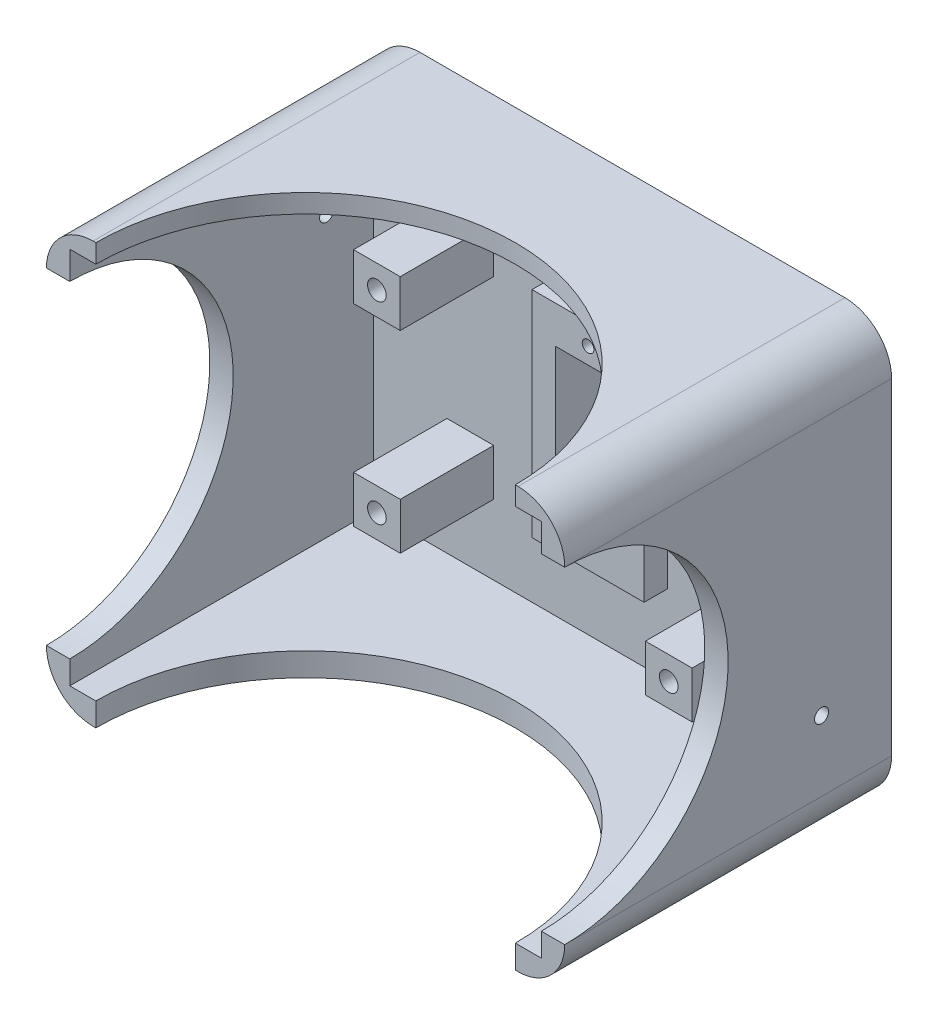
SolidWorks part; units mm, degrees
ref_plane "Plan de face" through (0, 0, 0) normal (0, 0, 1) x (1, 0, 0)
ref_plane "Plan de dessus" through (0, 0, 0) normal (0, 1, 0) x (1, 0, 0)
ref_plane "Plan de droite" through (0, 0, 0) normal (1, 0, 0) x (0, 0, -1)
sketch "Esquisse1" plane through (0, 0, 0) normal (0, 0, 1) x (1, 0, 0)
  line L0 (-192.776, 43.0961) -> (-152.776, 47.5961)
  line L1 (-152.776, 47.5961) -> (115.224, 47.5961)
  line L2 (-152.776, 47.5961) -> (-152.776, -102.4039)
  line L3 (-152.776, -102.4039) -> (115.224, -102.4039)
  line L4 (115.224, 47.5961) -> (115.224, -102.4039)
  line L5 (-152.776, 47.5961) -> (-192.776, 47.5961)
  line L6 (-152.776, 53.8314) -> (-152.776, -102.4039)
  line L7 (-152.776, 47.5961) -> (-152.776, -102.4039)
  line L8 (-152.776, -102.4039) -> (-192.776, -102.4039)
  line L9 (-192.776, 47.5961) -> (-192.776, -102.4039)
  line L10 (-152.776, 47.5961) -> (-192.776, 47.5961)
  line L11 (-152.776, 47.5961) -> (-152.776, 43.0961)
  line L12 (-152.776, 43.0961) -> (-192.776, 43.0961)
  line L13 (-192.776, 47.5961) -> (-192.776, 43.0961)
  line L14 (-152.776, -102.4039) -> (-192.776, -102.4039)
  line L15 (-152.776, -102.4039) -> (-152.776, -97.9039)
  line L16 (-152.776, -97.9039) -> (-192.776, -97.9039)
  line L17 (-192.776, -102.4039) -> (-192.776, -97.9039)
  line L18 (-192.776, -97.9039) -> (-152.776, -102.4039)
  line L20 (-106.994, -67.4039) -> (-5.994, -67.4039)
  line L21 (-106.994, -67.4039) -> (-106.994, 13.5961)
  line L22 (-106.994, 13.5961) -> (-5.994, 13.5961)
  line L23 (-5.994, -67.4039) -> (-5.994, 13.5961)
  line L24 (-144.9874, 47.5961) -> (-124.9874, 47.5961)
  line L25 (-144.9874, 47.5961) -> (-144.9874, 45.5961)
  line L26 (-144.9874, 45.5961) -> (-124.9874, 45.5961)
  line L27 (-124.9874, 47.5961) -> (-124.9874, 45.5961)
  line L28 (-144.9874, -102.4039) -> (-124.9874, -102.4039)
  line L29 (-144.9874, -102.4039) -> (-144.9874, -100.4039)
  line L30 (-144.9874, -100.4039) -> (-124.9874, -100.4039)
  line L31 (-124.9874, -102.4039) -> (-124.9874, -100.4039)
  line L32 (-111.994, -72.4039) -> (-0.994, -72.4039)
  line L33 (-111.994, -72.4039) -> (-111.994, 17.5961)
  line L34 (-111.994, 17.5961) -> (-0.994, 17.5961)
  line L35 (-0.994, -72.4039) -> (-0.994, 17.5961)
  line L36 (-101.994, 7.5961) -> (-10.994, 7.5961)
  line L37 (-101.994, 7.5961) -> (-101.994, -62.4039)
  line L38 (-101.994, -62.4039) -> (-10.994, -62.4039)
  line L39 (-10.994, 7.5961) -> (-10.994, -62.4039)
  line L40 (-48.994, -12.4039) -> (-62.994, -12.4039)
  line L41 (-48.994, -12.4039) -> (-48.994, -42.4039)
  line L42 (-48.994, -42.4039) -> (-62.994, -42.4039)
  line L43 (-62.994, -12.4039) -> (-62.994, -42.4039)
  line L44 (-101.994, 7.5961) -> (-91.994, 7.5961)
  line L45 (-101.994, 7.5961) -> (-101.994, -2.4039)
  line L46 (-91.2204, -1.1134) -> (-81.2204, -1.1134)
  line L47 (-91.2204, -1.1134) -> (-91.2204, -11.1134)
  line L48 (-101.994, -62.4039) -> (-91.994, -62.4039)
  line L49 (-101.994, -62.4039) -> (-101.994, -52.4039)
  line L50 (-91.2204, -11.1134) -> (-81.2204, -11.1134)
  line L51 (-81.2204, -1.1134) -> (-81.2204, -11.1134)
  line L52 (-10.994, -62.4039) -> (-20.994, -62.4039)
  line L53 (-10.994, -62.4039) -> (-10.994, -52.4039)
  line L54 (-28.7204, -1.16) -> (-18.7204, -1.16)
  line L55 (-28.7204, -1.16) -> (-28.7204, -11.16)
  line L56 (-10.994, 7.5961) -> (-20.994, 7.5961)
  line L57 (-10.994, 7.5961) -> (-10.994, -2.4039)
  line L58 (-28.7204, -11.16) -> (-18.7204, -11.16)
  line L59 (-18.7204, -1.16) -> (-18.7204, -11.16)
  line L60 (-67.994, -50.4039) -> (-43.994, -50.4039)
  line L61 (-67.994, -50.4039) -> (-67.994, -4.4039)
  line L62 (-67.994, -4.4039) -> (-43.994, -4.4039)
  line L63 (-43.994, -50.4039) -> (-43.994, -4.4039)
  line L64 (-28.7144, -42.46) -> (-18.7144, -42.46)
  line L65 (-28.7144, -42.46) -> (-28.7144, -52.46)
  line L66 (-28.7144, -52.46) -> (-18.7144, -52.46)
  line L67 (-18.7144, -42.46) -> (-18.7144, -52.46)
  line L68 (-91.2144, -42.4134) -> (-81.2144, -42.4134)
  line L69 (-91.2144, -42.4134) -> (-91.2144, -52.4134)
  line L70 (-91.2144, -52.4134) -> (-81.2144, -52.4134)
  line L71 (-81.2144, -42.4134) -> (-81.2144, -52.4134)
  arc A0 (115.224, -102.4039) -> (115.224, 47.5961) centre (-162.1791, -27.4039) ccw
  arc A1 (-192.776, -97.9039) -> (-192.776, 43.0961) centre (-63.7022, -27.4039) cw
  circle A2 centre (-215.7698, -27.1553) radius 2.5
  circle A3 centre (130.2178, -27.1553) radius 2.5
  circle A4 centre (-33.549, -107.4039) radius 2.5
  circle A5 centre (-33.549, 52.5961) radius 2.5
  circle A6 centre (-86.2204, -6.1134) radius 2
  circle A7 centre (-23.7204, -6.16) radius 2
  circle A8 centre (-86.2144, -47.4134) radius 2
  circle A9 centre (-23.7144, -47.46) radius 2
  circle A10 centre (-55.994, -45.9039) radius 1.25
  circle A11 centre (-55.994, -8.9039) radius 1.25
  point P11 (-210.776, -27.4039)
  point P12 (125.224, -27.4039)
  point P35 (-56.494, 17.5961)
  dimension "D10" = 30
  dimension "D19" = 5
  dimension "D48" = 62.5
  dimension "D60" = 37
  dimension "D1" = 268
  dimension "D2" = 150
  dimension "D3" = 40
  dimension "D4" = 4.5
  dimension "D5" = 4.5
  dimension "D6" = 18
  dimension "D7" = 75
  dimension "D8" = 10
  dimension "D9" = 75
  dimension "D11" = 81
  dimension "D12" = 35
  dimension "D13" = 48
  dimension "D14" = 2
  dimension "D15" = 20
  dimension "D16" = 20
  dimension "D17" = 2
  dimension "D18" = 48
  dimension "D20" = 30
  dimension "D21" = 5
  dimension "D22" = 5
  dimension "D23" = 5
  dimension "D24" = 34
  dimension "D25" = 101
  dimension "D26" = 5
  dimension "D27" = 5
  dimension "D28" = 10
  dimension "D29" = 5
  dimension "D30" = 5
  dimension "D31" = 5
  dimension "D32" = 14
  dimension "D33" = 30
  dimension "D34" = 38
  dimension "D35" = 10
  dimension "D36" = 5
  dimension "D37" = 5
  dimension "D38" = 10
  dimension "D39" = 10
  dimension "D40" = 5
  dimension "D41" = 5
  dimension "D42" = 10
  dimension "D43" = 20
  dimension "D44" = 5
  dimension "D45" = 8
  dimension "D46" = 5
  dimension "D47" = 8
  dimension "D49" = 62.5
  dimension "D50" = 41.3
  dimension "D51" = 41.3
  dimension "D52" = 62.5
  dimension "D53" = 10
  dimension "D54" = 5
  dimension "D55" = 5
  dimension "D56" = 10
  dimension "D57" = 10
  dimension "D58" = 5
  dimension "D59" = 5
  dimension "D61" = 7
  dimension "D62" = 3.5
  dimension "D63" = 7
extrude "Boss.-Extru.1" add sketch "Esquisse1" along normal blind 70 contours L32 L35 L34 L33 L23 L20 L21 L22 region at (-110.565, -27.4039, 0)
extrude "Boss.-Extru.2" add sketch "Esquisse1<35>" along normal blind 5 contours L20 L23 L22 L21 L36 L39 L38 L37 | L39 L36 L37 L38 region at (-105.6993, -26.9039, 0) region at (-96.994, 6.448, 0)
sketch "Esquisse1<35>" plane through (0, 0, 0) normal (0, 0, 1) x (1, 0, 0) same geometry as "Esquisse1"
extrude "Boss.-Extru.5" add sketch "Esquisse1<37>" along normal blind 1 contours L36 L37 region at (-96.994, 6.448, 0)
sketch "Esquisse1<37>" plane through (0, 0, 0) normal (0, 0, 1) x (1, 0, 0) same geometry as "Esquisse1"
extrude "Boss.-Extru.6" add sketch "Esquisse1<38>" along normal blind 5 contours L38 L37 | L38 L39 | L36 L39 region at (-96.994, 6.448, 0)
sketch "Esquisse1<38>" plane through (0, 0, 0) normal (0, 0, 1) x (1, 0, 0) same geometry as "Esquisse1"
fillet "Congé1" radius 10 1 edges at (-111.994, -72.4039, 35)
fillet "Congé2" radius 10 1 edges at (-111.994, 17.5961, 35)
fillet "Congé4" radius 10 1 edges at (-0.994, 17.5961, 35)
fillet "Congé5" radius 10 1 edges at (-0.994, -72.4039, 35)
sketch "Esquisse3" plane through (0, -72.4039, 0) normal (0, -1, 0) x (1, 0, 0)
  line L0 (-101.994, 70) -> (-10.994, 70) construction
  circle A0 centre (-56.494, 70) radius 44.9177
extrude "Enlèv. mat.-Extru.2" cut sketch "Esquisse3" against normal blind 111 contours A0
sketch "Esquisse4" plane through (-0.994, 0, 0) normal (1, 0, 0) x (0, 0, -1)
  line L0 (-70, -62.4039) -> (-70, 7.5961) construction
  circle A0 centre (-70, -27.4039) radius 35
extrude "Enlèv. mat.-Extru.3" cut sketch "Esquisse4" against normal blind 111 contours A0
sketch "Esquisse5" plane through (-111.994, 0, 0) normal (-1, 0, 0) x (0, 0, 1)
  line L0 (70, 7.5961) -> (0, 7.5961) construction
  line L1 (0, -62.4039) -> (0, 7.5961) construction
  circle A0 centre (15, -7.4039) radius 1.5
  dimension "D1" = 15
  dimension "D2" = 15
extrude "Enlèv. mat.-Extru.6" cut sketch "Esquisse5" against normal blind 5
sketch "Esquisse8" plane through (-0.994, 0, 0) normal (1, 0, 0) x (0, 0, -1)
  line L0 (-70, -62.4039) -> (0, -62.4039) construction
  line L1 (0, -62.4039) -> (0, 7.5961) construction
  circle A0 centre (-15, -47.4039) radius 1.5
  dimension "D1" = 15
  dimension "D2" = 15
extrude "Enlèv. mat.-Extru.7" cut sketch "Esquisse8" against normal blind 15 contours A0
extrude "Boss.-Extru.9" add sketch "Esquisse1<44>" along normal blind 10 contours L60 L63 L62 L61 L43 L40 L41 L42 region at (-67.4751, -27.4039, 0)
sketch "Esquisse1<44>" plane through (0, 0, 0) normal (0, 0, 1) x (1, 0, 0) same geometry as "Esquisse1"
extrude "Boss.-Extru.10" add sketch "Esquisse1<45>" along normal blind 25 contours L51 L46 L47 L50 A6 | L71 L68 L69 L70 A8 | L59 L54 L55 L58 A7 | L67 L64 L65 L66 A9 region at (-86.2204, -1.2548, 0) region at (-23.7204, -1.3014, 0) region at (-23.7144, -42.6014, 0) region at (-86.2144, -42.5548, 0)
sketch "Esquisse1<45>" plane through (0, 0, 0) normal (0, 0, 1) x (1, 0, 0) same geometry as "Esquisse1"
extrude "Boss.-Extru.11" add sketch "Esquisse1<46>" along normal blind 10 contours A8 | A6 | A7 | A9 | A7 region at (-86.2204, -6.1134, 0) region at (-23.7204, -6.16, 0) region at (-86.2144, -47.4134, 0) region at (-23.7144, -47.46, 0)
sketch "Esquisse1<46>" plane through (0, 0, 0) normal (0, 0, 1) x (1, 0, 0) same geometry as "Esquisse1"
extrude "Boss.-Extru.12" add sketch "Esquisse1<51>" along normal blind 5 contours A10 | A11 region at (-55.994, -45.9039, 0)
sketch "Esquisse1<51>" plane through (0, 0, 0) normal (0, 0, 1) x (1, 0, 0) same geometry as "Esquisse1"
